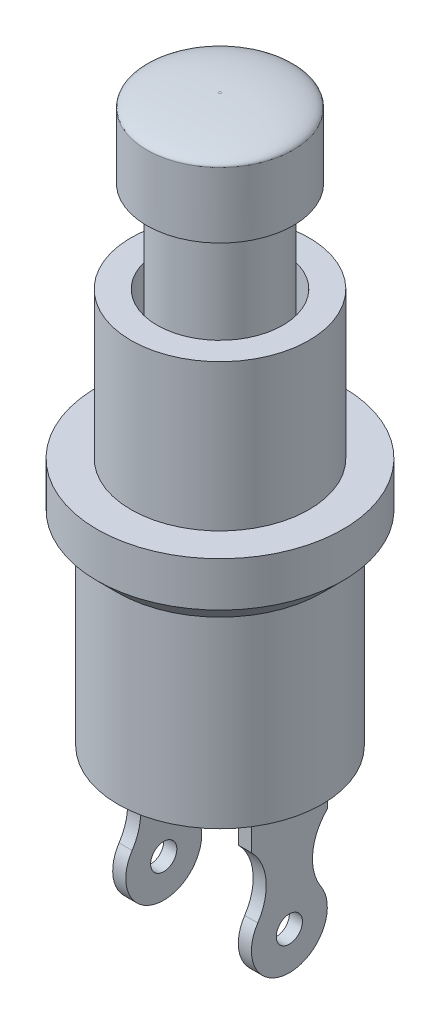
SolidWorks part; units mm, degrees
ref_plane "Front Plane" through (0, 0, 0) normal (0, 0, 1) x (1, 0, 0)
ref_plane "Top Plane" through (0, 0, 0) normal (0, 1, 0) x (1, 0, 0)
ref_plane "Right Plane" through (0, 0, 0) normal (1, 0, 0) x (0, 0, -1)
sketch "Sketch1" plane through (0, 0, 0) normal (0, 1, 0) x (1, 0, 0)
  circle A0 centre (0, 0) radius 3.9
  dimension "D1" = 7.8
extrude "Boss-Extrude1" add sketch "Sketch1" against normal blind 7
sketch "Sketch2" plane through (0, 0, 0) normal (0, 1, 0) x (1, 0, 0)
  circle A0 centre (0, 0) radius 4.7
  dimension "D1" = 9.4
extrude "Boss-Extrude2" add sketch "Sketch2" along normal blind 2.5
chamfer "Chamfer1" distance 0.8 angle 45 1 edges at (0, 0, 4.7)
sketch "Sketch3" plane through (0, 2.5, 0) normal (0, 1, 0) x (1, 0, 0)
  circle A0 centre (0, 0) radius 3.4
  circle A1 centre (0, 0) radius 2.4
  dimension "D1" = 6.8
  dimension "D2" = 1
extrude "Boss-Extrude3" add sketch "Sketch3" along normal blind 5.6
sketch "Sketch4" plane through (0, 2.5, 0) normal (0, 1, 0) x (1, 0, 0)
  circle A0 centre (0, 0) radius 2.05
  circle A1 centre (0, 0) radius 3.4 construction
  dimension "D1" = 1.35
extrude "Boss-Extrude4" add sketch "Sketch4" along normal blind 9.1
sketch "Sketch5" plane through (0, 11.6, 0) normal (0, 1, 0) x (1, 0, 0)
  circle A0 centre (0, 0) radius 2.8
  dimension "D1" = 5.6
extrude "Boss-Extrude5" add sketch "Sketch5" along normal blind 3
fillet "Fillet1" radius 0.5 1 edges at (0, 14.6, 2.8) second distance 2.75 first distance on face at (0, 14.6, 2.8)
sketch "Sketch6" plane through (0, -7, 0) normal (0, -1, 0) x (1, 0, 0)
  line L0 (-2.15, 0) -> (0, 0) construction
  line L1 (-2.65, 1.45) -> (-2.15, 1.45)
  line L2 (-2.65, 1.45) -> (-2.65, -1.45)
  line L3 (-2.65, -1.45) -> (-2.15, -1.45)
  line L4 (-2.15, 1.45) -> (-2.15, -1.45)
  line L5 (2.15, 1.45) -> (2.65, 1.45)
  line L6 (2.15, 1.45) -> (2.15, -1.45)
  line L7 (2.15, -1.45) -> (2.65, -1.45)
  line L8 (2.65, 1.45) -> (2.65, -1.45)
  line L9 (0, 0) -> (2.15, 0) construction
  dimension "D1" = 2.9
  dimension "D2" = 5.3
  dimension "D3" = 0.5
extrude "Boss-Extrude6" add sketch "Sketch6" along normal blind 6.2
sketch "Sketch7" plane through (0, 0, 0) normal (1, 0, 0) x (0, 0, -1)
  line L0 (1.45, -13.2) -> (1.45, -7) construction
  line L1 (1.45, -13.2) -> (-1.45, -13.2) construction
  line L2 (-1.45, -13.2) -> (-1.45, -7) construction
  line L3 (1.45, -7) -> (-1.45, -7) construction
  line L4 (-1.45, -8.5) -> (-1.45, -13.2)
  line L5 (-1.45, -13.2) -> (1.45, -13.2)
  line L6 (-1.45, -8.5) -> (1.45, -8.5) construction
  line L7 (-1.45, -8.5) -> (0, -9.95) construction
  line L8 (0, -9.95) -> (1.45, -8.5) construction
  line L9 (0, -9.95) -> (0, -11.75) construction
  line L10 (1.45, -13.2) -> (1.45, -8.5)
  arc A0 (-1.207, -10.9464) -> (1.207, -10.9464) centre (0, -11.75) ccw
  circle A1 centre (0, -11.75) radius 0.5
  arc A2 (-1.207, -10.9464) -> (-1.45, -8.5) centre (-2.8215, -9.8715) ccw
  arc A3 (1.45, -8.5) -> (1.207, -10.9464) centre (2.8215, -9.8715) ccw
  dimension "D1" = 1
  dimension "D2" = 1.5
extrude "Cut-Extrude1" cut sketch "Sketch7" against normal blind 6.2 and the other way blind 6.2 contours A0 A2 L4 | A0 L5 L10 | A0 L4 L5 | L10 A3 A0 | A1 | L5 L10 A3 A0 A2 L4 region at (0, -9.903, 1.2236) region at (0, -9.903, -1.2236) region at (0, -12.8761, -1.1261) region at (0, -12.8761, 1.1261)
